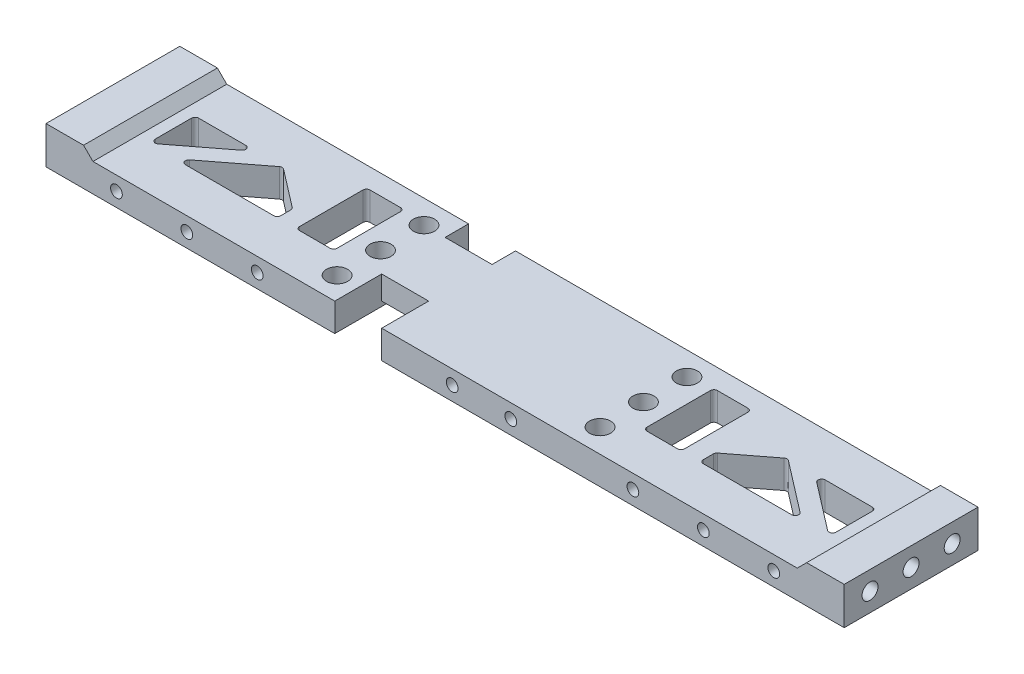
SolidWorks part; units mm, degrees
material "7075-T6, Chapa (SS)"
ref_plane "Plano frontal" through (0, 0, 0) normal (0, 0, 1) x (1, 0, 0)
ref_plane "Plano superior" through (0, 0, 0) normal (0, 1, 0) x (1, 0, 0)
ref_plane "Plano direito" through (0, 0, 0) normal (1, 0, 0) x (0, 0, -1)
sketch "Esboço1" plane through (0, 0, 0) normal (0, 1, 0) x (1, 0, 0)
  line L0 (170, 57) -> (170, 0) construction
  line L1 (0, 0) -> (340, 0)
  line L2 (0, 0) -> (0, 57)
  line L3 (0, 57) -> (340, 57)
  line L4 (340, 0) -> (340, 57)
  dimension "D1" = 57
  dimension "D2" = 340
extrude "Ressalto-extrusão1" add sketch "Esboço1" along normal blind 12
sketch "Esboço2" plane through (0, 12, 0) normal (0, 1, 0) x (1, 0, 0)
  line L0 (340, 57) -> (0, 57) construction
  line L1 (0, 0) -> (20, 0)
  line L2 (0, 0) -> (0, 57)
  line L3 (0, 57) -> (20, 57)
  line L4 (20, 0) -> (20, 57)
  line L5 (0, 0) -> (340, 0) construction
  line L6 (340, 57) -> (320, 57)
  line L7 (340, 57) -> (340, 0)
  line L8 (340, 0) -> (320, 0)
  line L9 (320, 57) -> (320, 0)
  dimension "D1" = 20
  dimension "D2" = 20
extrude "Ressalto-extrusão2" add sketch "Esboço2" along normal blind 4
hole_wizard "Broca de rosquear para tarraxa de M81" positions "Esboço3" profile "Esboço4" hole size "M8" standard "ISO"
sketch "Esboço3" plane through (0, 0, 0) normal (-1, 0, 0) x (0, 0, 1)
  line L0 (-57, 8) -> (-46, 8) construction
  line L1 (-57, 16) -> (-57, 0) construction
  line L2 (-46, 8) -> (-28.5, 8) construction
  line L3 (-28.5, 8) -> (-11, 8) construction
  line L4 (-11, 8) -> (0, 8) construction
  line L5 (0, 16) -> (0, 0) construction
  point P0 (-46, 8)
  point P2 (-28.5, 8)
  point P4 (-11, 8)
  dimension "D1" = 11
  dimension "D2" = 11
sketch "Esboço4" plane through (0, 8, -46) normal (0, 1, 0) x (0, 0, 1)
  line L0 (0, 0) -> (0, 17.0429)
  line L1 (0, 17.0429) -> (3.4, 15)
  line L2 (3.4, 15) -> (3.4, 0)
  line L5 (3.4, 0) -> (0, 0)
  line L10 (0, 17.0429) -> (-3.4, 15) construction
  line L11 (0, -6.35) -> (0, 107.95) construction
  dimension "Hole Dia." = 6.8
  dimension "Hole Depth" = 15
  dimension "Drill Angle" = 118
hole_wizard "Broca de rosquear para tarraxa de M82" positions "Esboço5" profile "Esboço6" hole size "M8" standard "ISO"
sketch "Esboço5" plane through (340, 0, 0) normal (1, 0, 0) x (0, 0, -1)
  line L0 (0, 8) -> (11, 8) construction
  line L1 (0, 16) -> (0, 0) construction
  line L2 (46, 8) -> (57, 8) construction
  line L3 (57, 16) -> (57, 0) construction
  line L5 (11, 8) -> (28.5, 8) construction
  line L6 (28.5, 8) -> (46, 8) construction
  point P1 (11, 8)
  point P4 (46, 8)
  point P19 (28.5, 8)
  dimension "D1" = 11
  dimension "D2" = 11
sketch "Esboço6" plane through (340, 8, -28.5) normal (0, 1, 0) x (0, 0, -1)
  line L0 (0, 0) -> (0, 17.0429)
  line L1 (0, 17.0429) -> (3.4, 15)
  line L2 (3.4, 15) -> (3.4, 0)
  line L5 (3.4, 0) -> (0, 0)
  line L10 (0, 17.0429) -> (-3.4, 15) construction
  line L11 (0, -6.35) -> (0, 107.95) construction
  dimension "Hole Dia." = 6.8
  dimension "Hole Depth" = 15
  dimension "Drill Angle" = 118
sketch "Esboço7" plane through (0, 12, 0) normal (0, 1, 0) x (1, 0, 0)
  line L0 (320, 57) -> (20, 57) construction
  line L1 (123, 57) -> (143, 57)
  line L2 (123, 57) -> (123, 47)
  line L3 (123, 47) -> (143, 47)
  line L4 (143, 57) -> (143, 47)
  line L5 (20, 0) -> (320, 0) construction
  line L6 (123, 0) -> (143, 0)
  line L7 (123, 0) -> (123, 20)
  line L8 (123, 20) -> (143, 20)
  line L9 (143, 0) -> (143, 20)
  line L10 (0, 57) -> (0, 0) construction
  dimension "D1" = 20
  dimension "D2" = 10
  dimension "D3" = 123
  dimension "D4" = 20
extrude "Corte-extrusão1" cut sketch "Esboço7" against normal through all
chamfer "Chanfro1" distance 2 angle 60 2 edges at (133, 0, -20) (133, 0, -47) first distance on face at (133, 6, -20) first distance on face at (133, 6, -47)
chamfer "Chanfro3" distance 4 angle 45 2 edges at (20, 16, -28.5) (320, 16, -28.5)
hole_wizard "Broca de rosquear para tarraxa de M61" positions "Esboço10" profile "Esboço11" hole size "M6" standard "ISO"
sketch "Esboço10" plane through (0, 0, -57) normal (0, 0, -1) x (-1, 0, 0)
  line L0 (-340, 6) -> (0, 6) construction
  line L1 (-340, 16) -> (-340, 0) construction
  line L2 (0, 16) -> (0, 0) construction
  line L4 (-340, 0) -> (-143, 0) construction
  line L5 (-143, 0) -> (-143, 12) construction
  point P0 (-310, 6)
  point P2 (-280, 6)
  point P4 (-30, 6)
  point P6 (-60, 6)
  point P32 (-264, 6)
  point P34 (-76, 6)
  point P37 (-198, 6)
  point P39 (-173, 6)
  dimension "D1" = 6
  dimension "D2" = 30
  dimension "D3" = 30
  dimension "D4" = 30
  dimension "D5" = 30
  dimension "D6" = 16
  dimension "D7" = 16
  dimension "D8" = 30
  dimension "D9" = 25
sketch "Esboço11" plane through (310, 6, -57) normal (1, 0, 0) x (0, 1, 0)
  line L0 (0, 0) -> (0, 16.5022)
  line L1 (0, 16.5022) -> (2.5, 15)
  line L2 (2.5, 15) -> (2.5, 0)
  line L5 (2.5, 0) -> (0, 0)
  line L10 (0, 16.5022) -> (-2.5, 15) construction
  line L11 (0, -6.35) -> (0, 107.95) construction
  dimension "Hole Dia." = 5
  dimension "Hole Depth" = 15
  dimension "Drill Angle" = 118
hole_wizard "Broca de rosquear para tarraxa de M62" positions "Esboço12" profile "Esboço13" hole size "M6" standard "ISO"
sketch "Esboço12" plane through (0, 0, 0) normal (0, 0, 1) x (1, 0, 0)
  line L0 (0, 6) -> (340, 6) construction
  line L1 (0, 16) -> (0, 0) construction
  line L2 (340, 16) -> (340, 0) construction
  line L4 (0, 0) -> (123, 0) construction
  line L5 (143, 0) -> (143, 12) construction
  point P0 (30, 6)
  point P2 (60, 6)
  point P4 (280, 6)
  point P6 (310, 6)
  point P34 (90, 6)
  point P36 (250, 6)
  point P37 (173, 6)
  point P39 (198, 6)
  dimension "D1" = 6
  dimension "D2" = 30
  dimension "D3" = 30
  dimension "D4" = 30
  dimension "D5" = 30
  dimension "D6" = 30
  dimension "D7" = 30
  dimension "D8" = 30
  dimension "D9" = 25
sketch "Esboço13" plane through (30, 6, 0) normal (1, 0, 0) x (0, -1, 0)
  line L0 (0, 0) -> (0, 16.5022)
  line L1 (0, 16.5022) -> (2.5, 15)
  line L2 (2.5, 15) -> (2.5, 0)
  line L5 (2.5, 0) -> (0, 0)
  line L10 (0, 16.5022) -> (-2.5, 15) construction
  line L11 (0, -6.35) -> (0, 107.95) construction
  dimension "Hole Dia." = 5
  dimension "Hole Depth" = 15
  dimension "Drill Angle" = 118
hole_wizard "Escareado para parafuso Allen sextavado escareado de M82" positions "Esboço16" profile "Esboço17" countersink size "M8" standard "ISO"
sketch "Esboço16" plane through (0, 0, 0) normal (0, -1, 0) x (-1, 0, 0)
  line L0 (-114, 47) -> (-114, 10) construction
  line L2 (-226, 47) -> (-226, 10) construction
  line L5 (-123, 57) -> (0, 57) construction
  line L6 (0, 0) -> (-123, 0) construction
  line L8 (-143, 0) -> (-340, 0) construction
  line L9 (-340, 57) -> (-143, 57) construction
  line L10 (0, 57) -> (0, 0) construction
  line L11 (-340, 0) -> (-340, 57) construction
  point P0 (-114, 47)
  point P2 (-114, 28.5)
  point P4 (-114, 10)
  point P6 (-226, 47)
  point P8 (-226, 28.5)
  point P10 (-226, 10)
  dimension "D1" = 114
  dimension "D2" = 10
  dimension "D3" = 10
  dimension "D4" = 114
  dimension "D5" = 10
  dimension "D6" = 10
sketch "Esboço17" plane through (114, 0, -47) normal (1, 0, 0) x (0, 0, -1)
  line L0 (0, 0) -> (0, 17.7039)
  line L1 (0, 17.7039) -> (4.5, 15)
  line L2 (4.5, 15) -> (4.5, 4.46)
  line L3 (4.5, 4.46) -> (8.96, 0)
  line L5 (8.96, 0) -> (0, 0)
  line L6 (-4.5, 4.46) -> (-8.96, 0) construction
  line L10 (0, 17.7039) -> (-4.5, 15) construction
  line L11 (0, -6.35) -> (0, 107.95) construction
  dimension "Hole Dia." = 9
  dimension "Hole Depth" = 15
  dimension "Near C'Sink Dia." = 17.92
  dimension "Near C'Sink Angle" = 90
  dimension "Drill Angle" = 118
sketch "Esboço18" plane through (0, 0, 0) normal (0, -1, 0) x (1, 0, 0)
  line L0 (99.7913, -40.3319) -> (13.7913, -7.3319) construction
  line L1 (10.2087, -40.3319) -> (96.2087, -7.3319) construction
  line L2 (96.2087, -49.6681) -> (10.2087, -16.6681) construction
  line L3 (13.7913, -49.6681) -> (99.7913, -16.6681) construction
  line L4 (157.5052, -49.3271) -> (214.5052, -16.3271) construction
  line L5 (209.4948, -49.3271) -> (152.4948, -16.3271) construction
  line L6 (152.4948, -40.6729) -> (209.4948, -7.6729) construction
  line L7 (214.5052, -40.6729) -> (157.5052, -7.6729) construction
  line L8 (329.7556, -40.3184) -> (241.7556, -7.3184) construction
  line L9 (238.2444, -40.3184) -> (326.2444, -7.3184) construction
  line L10 (326.2444, -49.6816) -> (238.2444, -16.6816) construction
  line L11 (241.7556, -49.6816) -> (329.7556, -16.6816) construction
  line L12 (155, -45) -> (155, -12)
  line L13 (172.4256, -45) -> (194.5744, -45)
  line L14 (328, -45) -> (328, -12)
  line L15 (302.7307, -12) -> (265.2693, -12)
  line L16 (98, -12) -> (98, -45)
  line L17 (12, -45) -> (111, -45) construction
  line L18 (73.2485, -12) -> (36.7515, -12)
  line L19 (12, -12) -> (12, -45)
  line L20 (36.7515, -45) -> (73.2485, -45)
  line L21 (111, -12) -> (12, -12) construction
  line L22 (240, -45) -> (240, -12)
  line L23 (212, -12) -> (212, -45)
  line L24 (143, -23.4641) -> (123, -23.4641)
  line L25 (123, -23.4641) -> (123, 0)
  line L26 (123, 0) -> (0, 0)
  line L27 (0, 0) -> (0, -57)
  line L28 (0, -57) -> (123, -57)
  line L29 (123, -57) -> (123, -43.5359)
  line L30 (123, -43.5359) -> (143, -43.5359)
  line L31 (143, -43.5359) -> (143, -57)
  line L32 (143, -57) -> (340, -57)
  line L33 (340, -57) -> (340, 0)
  line L34 (340, 0) -> (143, 0)
  line L35 (143, 0) -> (143, -23.4641)
  line L36 (143, -23.4641) -> (123, -23.4641)
  line L37 (123, -23.4641) -> (123, 0)
  line L38 (123, 0) -> (0, 0)
  line L39 (0, 0) -> (0, -57)
  line L40 (0, -57) -> (123, -57)
  line L41 (123, -57) -> (123, -43.5359)
  line L42 (123, -43.5359) -> (143, -43.5359)
  line L43 (143, -43.5359) -> (143, -57)
  line L44 (143, -57) -> (340, -57)
  line L45 (340, -57) -> (340, 0)
  line L46 (340, 0) -> (143, 0)
  line L47 (143, 0) -> (143, -23.4641)
  line L48 (265.2693, -45) -> (302.7307, -45)
  line L49 (155, -12) -> (155, -23.4641) construction
  line L50 (155, -43.5359) -> (155, -45) construction
  line L51 (111, -45) -> (111, -43.5359) construction
  line L52 (111, -23.4641) -> (111, -12) construction
  line L53 (155, -45) -> (328, -45) construction
  line L54 (194.5744, -12) -> (172.4256, -12)
  line L55 (328, -12) -> (155, -12) construction
  line L56 (328, -45) -> (240, -12)
  line L57 (240, -45) -> (328, -12)
  line L58 (212, -45) -> (155, -12)
  line L59 (155, -45) -> (212, -12)
  line L60 (98, -45) -> (12, -12)
  line L61 (12, -45) -> (98, -12)
  line L62 (264.5671, -41.1273) -> (329.7556, -16.6816)
  line L63 (329.7556, -40.3184) -> (264.5671, -15.8727)
  line L64 (214.5052, -40.6729) -> (171.4235, -15.7309)
  line L65 (171.4235, -41.2691) -> (214.5052, -16.3271)
  line L66 (36.035, -41.1327) -> (99.7913, -16.6681)
  line L67 (99.7913, -40.3319) -> (36.035, -15.8673)
  line L68 (238.2444, -40.3184) -> (303.4329, -15.8727)
  line L69 (303.4329, -41.1273) -> (238.2444, -16.6816)
  line L70 (195.5765, -41.2691) -> (152.4948, -16.3271)
  line L71 (152.4948, -40.6729) -> (195.5765, -15.7309)
  line L72 (10.2087, -40.3319) -> (73.965, -15.8673)
  line L73 (73.965, -41.1327) -> (10.2087, -16.6681)
  arc A0 (36.035, -15.8673) -> (36.7515, -12) centre (36.7515, -14) cw
  arc A1 (73.2485, -12) -> (73.965, -15.8673) centre (73.2485, -14) cw
  arc A2 (73.2485, -45) -> (73.965, -41.1327) centre (73.2485, -43) ccw
  arc A3 (36.7515, -45) -> (36.035, -41.1327) centre (36.7515, -43) cw
  arc A4 (172.4256, -45) -> (171.4235, -41.2691) centre (172.4256, -43) cw
  arc A5 (194.5744, -45) -> (195.5765, -41.2691) centre (194.5744, -43) ccw
  arc A6 (194.5744, -12) -> (195.5765, -15.7309) centre (194.5744, -14) cw
  arc A7 (171.4235, -15.7309) -> (172.4256, -12) centre (172.4256, -14) cw
  arc A8 (264.5671, -15.8727) -> (265.2693, -12) centre (265.2693, -14) cw
  arc A9 (302.7307, -12) -> (303.4329, -15.8727) centre (302.7307, -14) cw
  arc A10 (302.7307, -45) -> (303.4329, -41.1273) centre (302.7307, -43) ccw
  arc A11 (265.2693, -45) -> (264.5671, -41.1273) centre (265.2693, -43) cw
  dimension "D8" = 2
  dimension "D3" = 88
  dimension "D4" = 57
  dimension "D5" = 86
  dimension "D1" = 0
  dimension "D2" = 12
  dimension "D6" = 5
  dimension "D7" = 5
extrude "Corte-extrusão2" [suppressed] cut sketch "Esboço18" against normal through all contours L48 L69 L62 | L68 L69 L22 | L63 L14 L62 | L63 L68 L15 | L64 L71 L54 | L65 L64 L23 | L13 L70 L65 | L12 L71 L70 | L20 L73 L66 | L72 L73 L19 | L67 L16 L66 | L67 L72 L18
fillet "Filete1" [suppressed] radius 3
fillet "Filete4" [suppressed] radius 8
fillet "Filete5" [suppressed] radius 3
sketch "Esboço19" plane through (0, 0, 0) normal (0, -1, 0) x (1, 0, 0)
  line L0 (25, -18.5) -> (25, -38.5)
  line L1 (25, -38.5) -> (51, -38.5)
  line L2 (51, -38.5) -> (25, -18.5)
  line L3 (36.4809, -18.5) -> (62.4809, -38.5)
  line L5 (62.4809, -18.5) -> (36.4809, -18.5)
  line L9 (62.4809, -18.5) -> (62.4809, -38.5) construction
  line L10 (0, -57) -> (0, 0) construction
  line L11 (62.4809, -38.5) -> (80, -25.0237)
  line L12 (104, -18.5) -> (104, -48.5)
  line L13 (104, -48.5) -> (88, -48.5)
  line L14 (62.4809, -18.5) -> (62.4809, 0) construction
  line L24 (170, 0) -> (170, -57) construction
  line L25 (0, 0) -> (123, 0) construction
  line L26 (62.4809, -57) -> (62.4809, -38.5) construction
  line L27 (123, -57) -> (0, -57) construction
  line L28 (88, -48.5) -> (88, -18.5)
  line L29 (88, -18.5) -> (104, -18.5)
  line L31 (80, -25.0237) -> (80, -18.5)
  line L32 (80, -18.5) -> (62.4809, -18.5)
  line L33 (123, -23.4641) -> (123, 0) construction
  line L34 (96, -18.5) -> (96, 0) construction
  line L36 (143, 0) -> (340, 0) construction
  line L37 (340, -57) -> (143, -57) construction
  line L38 (252, -18.5) -> (236, -18.5)
  line L39 (252, -48.5) -> (252, -18.5)
  line L40 (236, -48.5) -> (252, -48.5)
  line L41 (236, -18.5) -> (236, -48.5)
  line L42 (260, -25.0237) -> (260, -18.5)
  line L43 (277.5191, -38.5) -> (260, -25.0237)
  line L44 (303.5191, -18.5) -> (277.5191, -38.5)
  line L45 (277.5191, -18.5) -> (303.5191, -18.5)
  line L46 (260, -18.5) -> (277.5191, -18.5)
  line L47 (315, -38.5) -> (289, -38.5)
  line L48 (315, -18.5) -> (315, -38.5)
  line L49 (289, -38.5) -> (315, -18.5)
  line L50 (340, 0) -> (340, -57) construction
  arc A0 (54.4404, -32.315) -> (62.4809, -28.3559) centre (62.4809, -38.5) cw construction
  arc A1 (62.4809, -28.3559) -> (70.5213, -32.315) centre (62.4809, -38.5) cw construction
  dimension "D1" = 25
  dimension "D2" = 19
  dimension "D3" = 16
  dimension "D4" = 7
  dimension "D5" = 26
  dimension "D7" = 25
  dimension "D8" = 18.5
  dimension "D6" = 8
  dimension "D9" = 18.5
  dimension "D10" = 30
extrude "Corte-extrusão3" cut sketch "Esboço19" against normal through all
fillet "Filete6" radius 1.5 22 edges at (104, 6, -48.5) (104, 6, -18.5) (88, 6, -18.5) (88, 6, -48.5) (315, 6, -38.5) (315, 6, -18.5) (289, 6, -38.5) (303.5191, 6, -18.5) (260, 6, -18.5) (260, 6, -25.0237) (277.5191, 6, -38.5) (252, 6, -48.5) (252, 6, -18.5) (236, 6, -48.5) (236, 6, -18.5) (36.4809, 6, -18.5) (80, 6, -18.5) (80, 6, -25.0237) (62.4809, 6, -38.5) (51, 6, -38.5) (25, 6, -38.5) (25, 6, -18.5)
